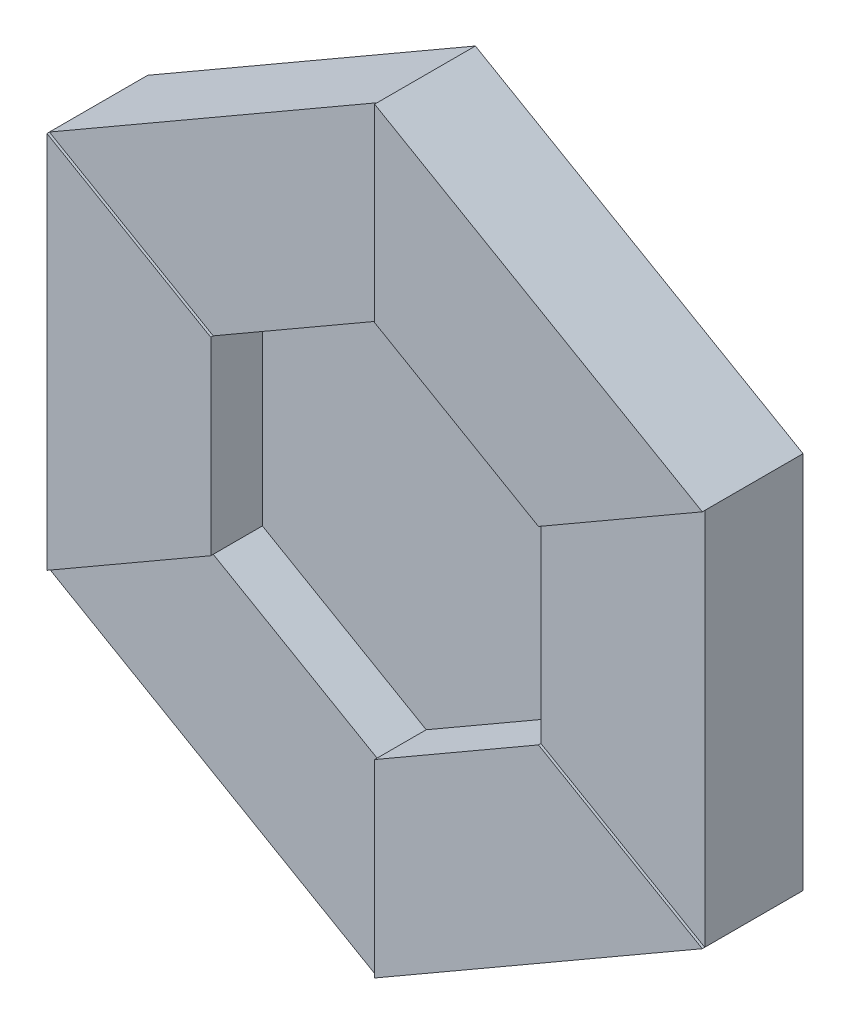
SolidWorks part; units mm, degrees
ref_plane "Front Plane" through (0, 0, 0) normal (0, 0, 1) x (1, 0, 0)
ref_plane "Top Plane" through (0, 0, 0) normal (0, 1, 0) x (1, 0, 0)
ref_plane "Right Plane" through (0, 0, 0) normal (1, 0, 0) x (0, 0, -1)
sketch "Sketch1" plane through (0, 0, 0) normal (0, 0, 1) x (1, 0, 0)
  line L0 (0, 0) -> (200, 115.4701) construction
  line L1 (200, -115.4701) -> (200, 115.4701)
  line L2 (200, 115.4701) -> (100, 57.735)
  line L3 (100, 57.735) -> (100, -57.735)
  line L4 (200, -115.4701) -> (100, -57.735)
  line L5 (0, 0) -> (200, -115.4701) construction
  line L6 (0, 0) -> (200, 0) construction
  dimension "D1" = 200
  dimension "D2" = 100
  dimension "D3" = 30
extrude "Boss-Extrude1" add sketch "Sketch1" along normal blind 30
ref_axis "Axis1" through (0, 0, -1.5) along (0, 0, 1)
move or copy body "Body-Move/Copy1" bodies to move or copy 101 copy yes number of copies 1 rotation origin (0, 0, 0) rotation axis (0, 0, 1) rotation angle 60
scale "Scale1" bodies to scale 103 scale about centroid uniform scaling no x scale factor 1 y scale factor 1 z scale factor 1.1
combine bodies "Combine1" operation type add bodies to combine 104 101
pattern_circular "CirPattern2" count 3 every 120 about axis through (0, 0, -1.5) along (0, 0, 1) of bodies 105
sketch "Sketch2" plane through (0, 0, 0) normal (0, 0, -1) x (-1, 0, 0)
  line L0 (-200, 115.4701) -> (0, 230.9401) construction
  line L1 (0, 230.9401) -> (200, 115.4701) construction
  line L2 (200, 115.4701) -> (200, -115.4701) construction
  line L3 (200, -115.4701) -> (0, -230.9401) construction
  line L4 (0, -230.9401) -> (-200, -115.4701) construction
  line L5 (-200, -115.4701) -> (-200, 115.4701) construction
  line L6 (-200, 115.4701) -> (0, 230.9401)
  line L7 (0, 230.9401) -> (200, 115.4701)
  line L8 (200, 115.4701) -> (200, -115.4701)
  line L9 (200, -115.4701) -> (0, -230.9401)
  line L10 (0, -230.9401) -> (-200, -115.4701)
  line L11 (-200, -115.4701) -> (-200, 115.4701)
extrude "Boss-Extrude3" add sketch "Sketch2" along normal blind 30
